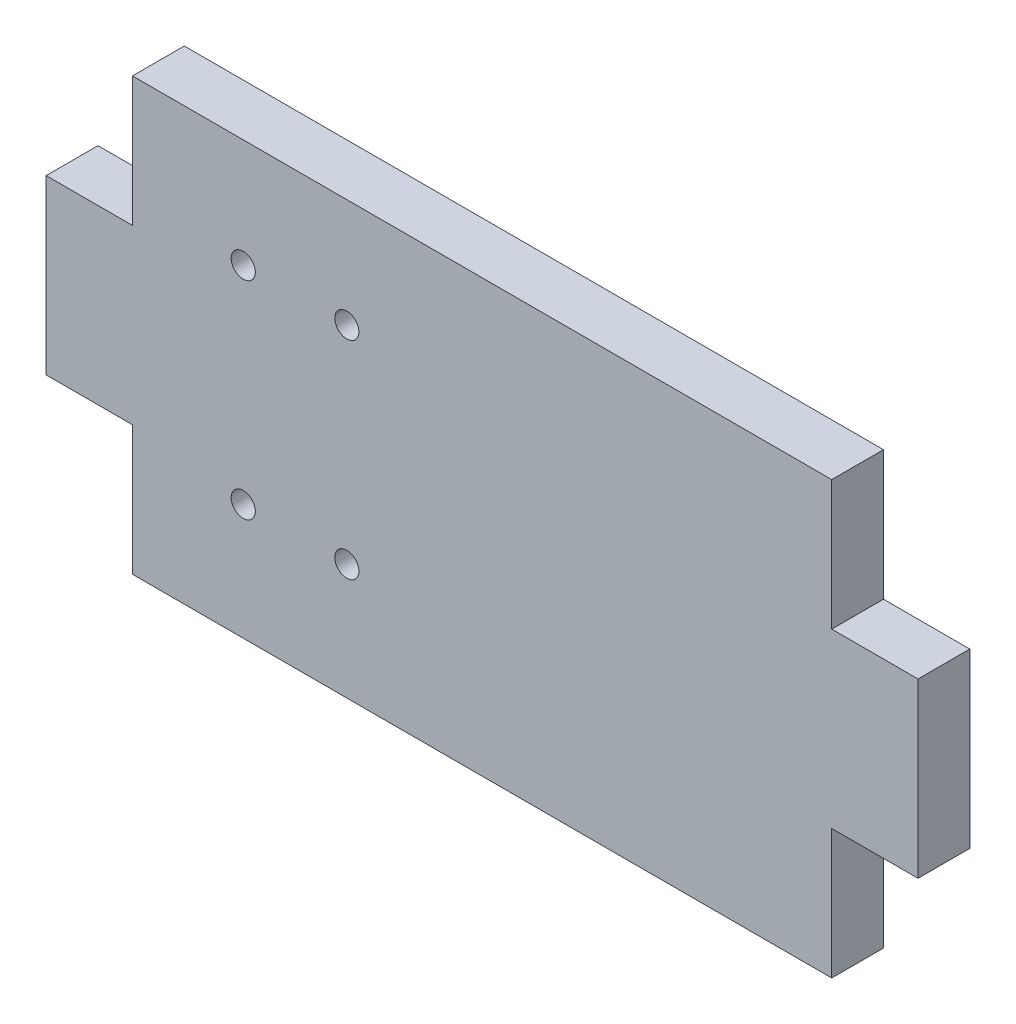
SolidWorks part; units mm, degrees
ref_plane "Plan de face" through (0, 0, 0) normal (0, 0, 1) x (1, 0, 0)
ref_plane "Plan de dessus" through (0, 0, 0) normal (0, 1, 0) x (1, 0, 0)
ref_plane "Plan de droite" through (0, 0, 0) normal (1, 0, 0) x (0, 0, -1)
sketch "Esquisse1" plane through (0, 0, 0) normal (0, 0, 1) x (1, 0, 0)
  line L1 (0, 0) -> (81, 0)
  line L2 (0, 0) -> (0, 50)
  line L3 (0, 50) -> (81, 50)
  line L4 (81, 0) -> (81, 50)
  line L5 (0, 35) -> (-10, 35)
  line L6 (0, 35) -> (0, 15)
  line L7 (0, 15) -> (-10, 15)
  line L8 (-10, 35) -> (-10, 15)
  line L9 (81, 35) -> (91, 35)
  line L10 (81, 35) -> (81, 15)
  line L11 (81, 15) -> (91, 15)
  line L12 (91, 35) -> (91, 15)
  point P13 (-10, 25)
  point P14 (0, 25)
  point P15 (91, 25)
  point P16 (81, 25)
  dimension "D1" = 81
  dimension "D2" = 50
  dimension "D3" = 10
  dimension "D4" = 20
  dimension "D5" = 10
  dimension "D6" = 20
extrude "Boss.-Extru.1" add sketch "Esquisse1" along normal blind 6 contours L5 L8 L7 L2 | L1 L4 L3 L2 | L12 L9 L4 L11 region at (40.5, 25, 0) region at (-5, 25, 0) region at (86, 25, 0)
sketch "Esquisse2" plane through (0, 0, 0) normal (0, 0, -1) x (-1, 0, 0)
  line L0 (-24.8289, 37.4224) -> (-12.8289, 37.4224) construction
  line L1 (-12.8289, 37.4224) -> (-12.8289, 13.4224) construction
  line L2 (-12.8289, 13.4224) -> (-24.8289, 13.4224) construction
  line L3 (-24.8289, 13.4224) -> (-24.8289, 37.4224) construction
  circle A0 centre (-12.8289, 13.4224) radius 1.4
  circle A1 centre (-12.8289, 37.4224) radius 1.4
  circle A2 centre (-24.8289, 37.4224) radius 1.4
  circle A3 centre (-24.8289, 13.4224) radius 1.4
  arc A4 (-11.7789, 37.4224) -> (-13.8789, 37.4224) centre (-12.8289, 37.4224) ccw construction
  point P2 (-35.7047, 22.1956)
  point P5 (-12.8851, 40.9667)
  point P8 (0, 0)
  dimension "D1" = 2.8
  dimension "D2" = 2.8
  dimension "D3" = 2.8
  dimension "D4" = 2.8
  dimension "D5" = 24
  dimension "D6" = 12
extrude "Enlèv. mat.-Extru.1" cut sketch "Esquisse2" against normal up to surface (6 mm away) up to face at (40.5, 25, 6)
sketch "Esquisse3" plane through (0, 0, 0) normal (0, 0, -1) x (-1, 0, 0)
  circle A0 centre (-24.8289, 37.4224) radius 3
  circle A1 centre (-12.8289, 37.4224) radius 3
  circle A2 centre (-12.8289, 13.4224) radius 3
  circle A3 centre (-24.8289, 13.4224) radius 3
  dimension "D1" = 6
extrude "Enlèv. mat.-Extru.2" cut sketch "Esquisse3" against normal blind 4
